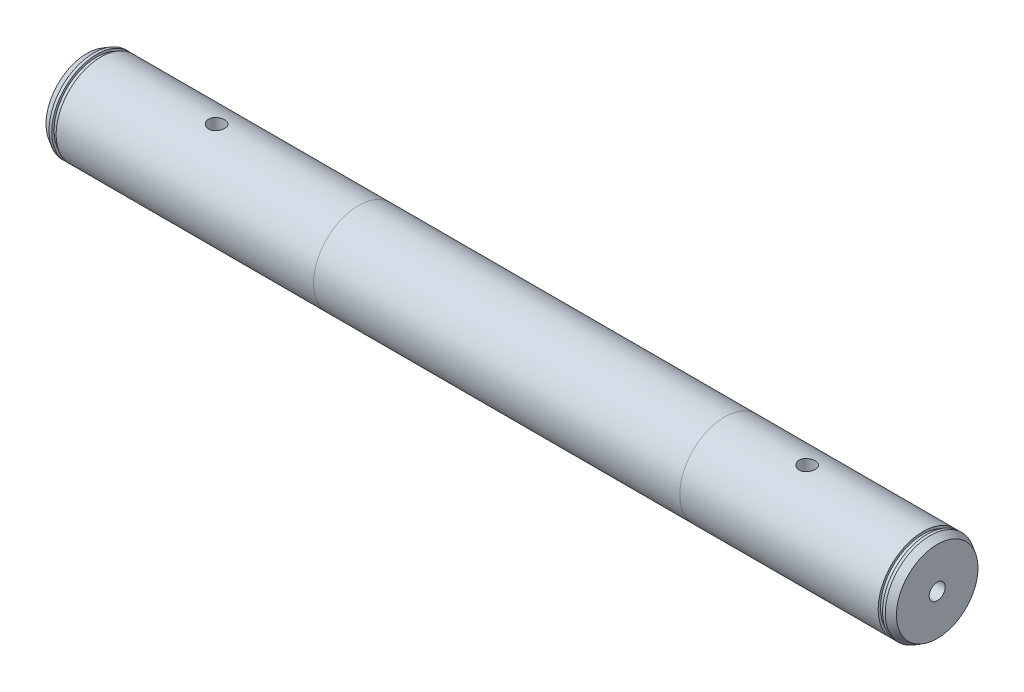
SolidWorks part; units mm, degrees
material "1.7225 (42CrMo4)"
ref_plane "E_Oben" through (0, 0, 0) normal (0, 0, 1) x (1, 0, 0)
ref_plane "E_Vorne" through (0, 0, 0) normal (0, 1, 0) x (1, 0, 0)
ref_plane "E_Rechts" through (0, 0, 0) normal (1, 0, 0) x (0, 0, -1)
ref_axis "A_Drehachse" through (-88.99, 0, 0) along (1, 0, 0)
sketch "Skizze1" plane through (0, 0, 0) normal (0, 0, 1) x (1, 0, 0)
  line L1 (0, -55) -> (0, 55) construction
  line L3 (180, 19) -> (180, 0)
  line L4 (180, 0) -> (-180, 0)
  line L7 (-180, 19) -> (-180, 0)
  line L10 (-65, 19) -> (-65, 27)
  line L11 (-65, 27) -> (-60, 27)
  line L12 (-60, 27) -> (-60, 19.0001)
  line L13 (-180, 19) -> (-65, 19)
  line L14 (-60, 19.0001) -> (90, 19.0001)
  line L15 (90, 19.0001) -> (90, 19)
  line L16 (90, 19) -> (180, 19)
  point P12 (0, 0)
  point P19 (-62.5, 27)
  dimension "D1" = 19.0001
  dimension "D2" = 19
  dimension "D3" = 19
  dimension "D4" = 360
  dimension "D5" = 115
  dimension "D6" = 5
  dimension "D7" = 27
  dimension "D8" = 150
revolve "Rotation1" add sketch "Skizze1" angle 360 about L4
hole_wizard "M8 Gewindebohrung1" positions "Skizze13" profile "Skizze14" tap size "M8" standard "DIN"
sketch "Skizze13" plane through (180, 0, 0) normal (1, 0, 0) x (0, 0, -1)
  point P0 (0, 0)
  point P3 (0, 0)
sketch "Skizze14" plane through (180, 0, 0) normal (0, 1, 0) x (0, 0, -1)
  line L0 (0, 0) -> (0, 327.0429)
  line L1 (0, 327.0429) -> (3.4, 325)
  line L2 (3.4, 325) -> (3.4, 0)
  line L5 (3.4, 0) -> (0, 0)
  line L10 (0, 327.0429) -> (-3.4, 325) construction
  line L11 (0, -6.35) -> (0, 107.95) construction
  dimension "Bohrerdurchmesser" = 6.8
  dimension "Bohrungstiefe" = 325
  dimension "Spitzenwinkel" = 118
cosmetic thread "Bohrungsgewinde2" parameters "D1"=20, "D2"=8
hole_wizard "M8 Gewindebohrung3" positions "Skizze17" profile "Skizze18" tap size "M8" standard "DIN" end condition through all
sketch "Skizze17" plane through (0, 0, 0) normal (0, 1, 0) x (1, 0, 0)
  line L0 (-55, 0) -> (55, 0) construction
  line L1 (-88.99, 0) -> (88.99, 0) construction
  line L3 (180, -19) -> (180, 19) construction
  point P0 (-125, 0)
  point P4 (125, 0)
  dimension "D3" = 305
  dimension "D4" = 55
sketch "Skizze18" plane through (-125, 0, 0) normal (1, 0, 0) x (0, 0, -1)
  line L0 (0, 0) -> (0, 27)
  line L1 (0, 27) -> (3.4, 27)
  line L2 (3.4, 27) -> (3.4, 0)
  line L5 (3.4, 0) -> (0, 0)
  line L11 (0, -6.35) -> (0, 107.95) construction
  dimension "Bohrerdurchmesser" = 6.8
  dimension "Bohrungstiefe" = 27
mirror "Spiegeln2" about plane through (0, 0, 0) normal (0, 1, 0) of "M8 Gewindebohrung3"
sketch "Skizze19" plane through (0, 0, 0) normal (0, 0, 1) x (1, 0, 0)
  line L0 (180, -19) -> (180, 19) construction
  line L8 (180, 19) -> (128.4, 19) construction
  line L9 (174, 19) -> (175.85, 19)
  line L10 (174, 19) -> (174, 18)
  line L11 (174, 18) -> (175.85, 18)
  line L12 (175.85, 19) -> (175.85, 18)
  dimension "D1" = 6
  dimension "D2" = 1
  dimension "D4" = 1.85
revolve "Schnitt-Rotation1" cut sketch "Skizze19" angle 360 about axis through (-88.99, 0, 0) along (1, 0, 0)
sketch "Skizze20" plane through (0, 0, 0) normal (0, 0, 1) x (1, 0, 0)
  line L0 (-180, 19) -> (-180, -19) construction
  line L9 (-128.3999, 19) -> (-180, 19) construction
  line L11 (-175.85, 19) -> (-174, 19)
  line L12 (-175.85, 19) -> (-175.85, 18)
  line L13 (-175.85, 18) -> (-174, 18)
  line L14 (-174, 19) -> (-174, 18)
  dimension "D1" = 6
  dimension "D4" = 1
  dimension "D5" = 1.85
revolve "Schnitt-Rotation2" cut sketch "Skizze20" angle 360 about axis through (-88.99, 0, 0) along (1, 0, 0)
sketch "Sketch1" plane through (0, 0, 0) normal (0, 0, 1) x (1, 0, 0)
  line L0 (90, 19.0001) -> (-60, 19.0001) construction
  line L1 (-73.5073, 34.0844) -> (-52.0997, 34.0844)
  line L2 (-73.5073, 34.0844) -> (-73.5073, 19.0001)
  line L3 (-73.5073, 19.0001) -> (-52.0997, 19.0001)
  line L4 (-52.0997, 34.0844) -> (-52.0997, 19.0001)
  line L5 (180, -19) -> (180, 19) construction
  line L6 (-202.2322, 0) -> (240.1237, 0) construction
  dimension "D1" = 19.0001
  dimension "D2" = 21.4076
  dimension "D3" = 15.0843
  dimension "D4" = 232.0997
revolve "Cut-Revolve1" cut sketch "Sketch1" angle 360 about L6
chamfer "倒角1" distance 3 angle 30 2 edges at (-180, 0, -19) (180, 0, -19) first distance on face at (-180, 0, -19) first distance on face at (180, 0, -19)
